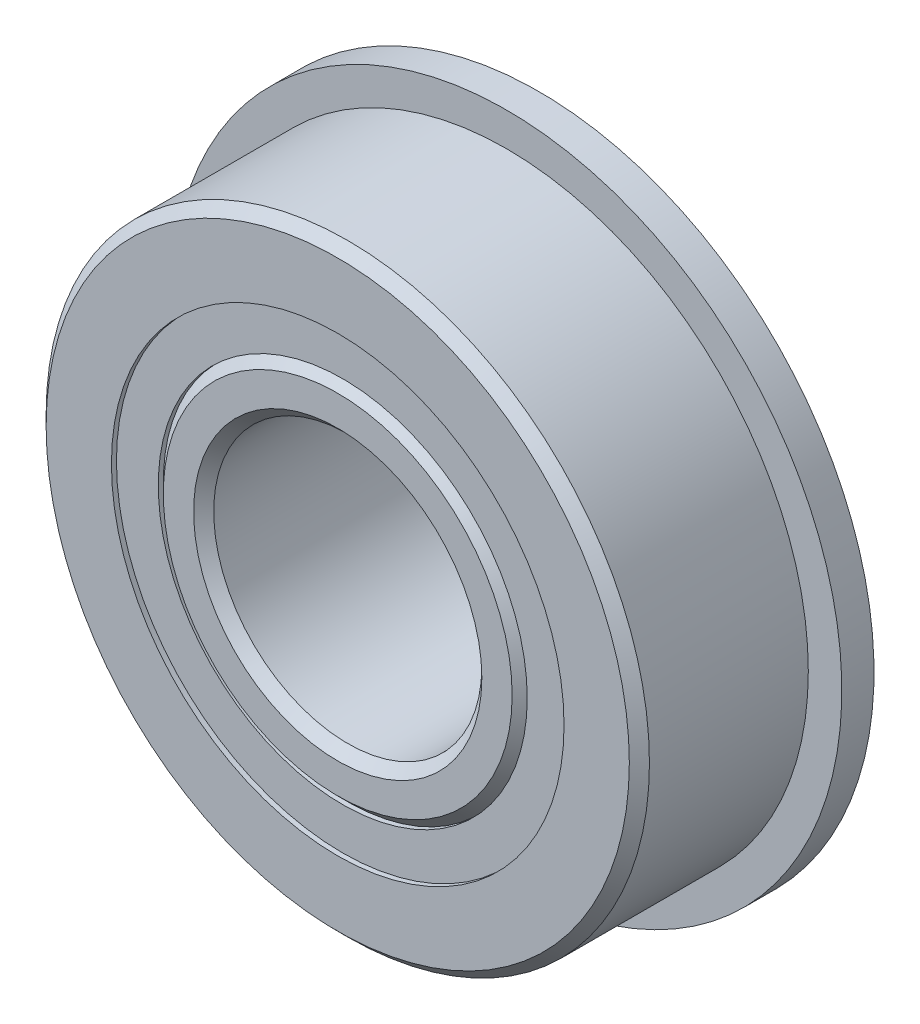
SolidWorks part; units mm, degrees
ref_plane "Front Plane" through (0, 0, 0) normal (0, 0, 1) x (1, 0, 0)
ref_plane "Top Plane" through (0, 0, 0) normal (0, 1, 0) x (1, 0, 0)
ref_plane "Right Plane" through (0, 0, 0) normal (1, 0, 0) x (0, 0, -1)
sketch "Sketch1" plane through (0, 0, 0) normal (1, 0, 0) x (0, 0, -1)
  line L0 (-4.7625, 0) -> (4.7625, 0) construction
  line L1 (0, 14.2875) -> (0, -14.2875) construction
  line L2 (4.2863, 14.2875) -> (-4.2862, 14.2875)
  line L3 (-4.2862, 14.2875) -> (-4.7625, 13.8112)
  line L4 (-4.7625, 13.8112) -> (-4.7625, 10.7188)
  line L5 (-4.7625, 10.7188) -> (-2.3474, 10.7188)
  line L6 (4.7625, 10.7188) -> (2.3474, 10.7188)
  line L7 (4.7625, 13.8112) -> (4.7625, 10.7188)
  line L8 (4.2863, 14.2875) -> (4.7625, 13.8112)
  line L9 (0, 14.2875) -> (0, 10.3187) construction
  line L10 (0, 10.3187) -> (0, 6.35) construction
  line L11 (4.7625, 8.7376) -> (4.7625, -8.7376) construction
  line L12 (-4.7625, 6.35) -> (4.7625, 6.35) construction
  line L13 (0, 7.9375) -> (0, 6.35) construction
  line L14 (0, 12.7) -> (0, 14.2875) construction
  line L15 (4.7625, 8.7376) -> (0, 8.7376) construction
  circle A1 centre (0, 10.3187) radius 2.3813 construction
  arc A2 (-2.3474, 10.7188) -> (2.3474, 10.7188) centre (0, 10.3187) cw
  point P14 (0, 6.35)
  point P22 (0, 7.9375)
  point P23 (0, 12.7)
  dimension "D3" = 4.7625
  dimension "Width" = 9.525
  dimension "OD" = 28.575
  dimension "D1" = 45
  dimension "D2" = 0.4763
  dimension "D4" = 17.4752
  dimension "D5" = 3.9624
  dimension "D6" = 1.9812
revolve "Revolve1" add sketch "Sketch1" angle 360 about L0
sketch "Sketch3" plane through (0, 0, 0) normal (1, 0, 0) x (0, 0, -1)
  line L1 (-4.7625, 13.8112) -> (-4.7625, 10.7188) construction
  line L2 (-4.2862, 14.2875) -> (-4.7625, 13.8112) construction
  line L3 (-4.7625, 9.9187) -> (-4.7625, 6.8262) construction
  line L4 (-4.7625, 6.8262) -> (-4.7625, 8.2614)
  line L5 (-4.7625, 6.8262) -> (-4.2862, 6.35)
  line L6 (-4.2862, 6.35) -> (5.8865, 6.35)
  line L7 (-4.7625, 13.8112) -> (-4.7625, -13.8112) construction
  line L8 (5.8865, 6.35) -> (6.3627, 6.8262)
  line L9 (0, 0) -> (6.3627, 0) construction
  line L13 (4.2863, 14.2875) -> (4.7625, 13.8112) construction
  line L14 (-4.7625, 8.2614) -> (-4.2862, 8.7376)
  line L15 (-4.2862, 8.7376) -> (-1.7805, 8.7376)
  line L16 (1.7805, 8.7376) -> (5.8865, 8.7376)
  line L17 (5.8865, 8.7376) -> (6.3627, 8.2614)
  line L18 (6.3627, 8.2614) -> (6.3627, 6.8262)
  circle A0 centre (0, 10.3187) radius 2.3812 construction
  arc A1 (-1.7805, 8.7376) -> (1.7805, 8.7376) centre (0, 10.3187) ccw
  dimension "D1" = 45
  dimension "Ring Wd" = 11.1252
  dimension "Inner Ring OD" = 17.4752
revolve "Revolve3" add sketch "Sketch3" angle 360 about L0
sketch "Sketch6" plane through (0, 0, 0) normal (1, 0, 0) x (0, 0, -1)
  line L1 (4.7625, 10.7188) -> (3.2385, 10.7188)
  line L2 (4.7625, 10.7188) -> (4.7625, 15.875)
  line L3 (4.7625, 15.875) -> (3.2385, 15.875)
  line L4 (3.2385, 10.7188) -> (3.2385, 15.875)
  line L5 (4.7625, 0) -> (-4.7625, 0) construction
  dimension "Flange OD" = 31.75
  dimension "Flange Thickness" = 1.524
revolve "Revolve6" add sketch "Sketch6" angle 360 about L5
sketch "Sketch4" plane through (0, 0, 0) normal (1, 0, 0) x (0, 0, -1)
  line L0 (-2.3813, 10.3187) -> (2.3813, 10.3187)
  circle A0 centre (0, 10.3187) radius 2.3812 construction
  arc A1 (2.3813, 10.3187) -> (-2.3813, 10.3187) centre (0, 10.3187) ccw
revolve "Revolve4" add sketch "Sketch4" angle 360 about L0
ref_axis "Axis1" through (0, 0, -4.7625) along (0, 0, 1)
pattern_circular "CirPattern1" count 12 every 30 about axis through (0, 0, -4.7625) along (0, 0, 1) of bodies 104
sketch "Sketch5" plane through (0, 0, 0) normal (1, 0, 0) x (0, 0, -1)
  line L0 (-4.7625, 10.7188) -> (-2.3474, 10.7188) construction
  line L1 (-4.5244, 10.7188) -> (-1.7805, 10.7188)
  line L2 (-4.5244, 10.7188) -> (-4.5244, 8.7376)
  line L3 (-4.5244, 8.7376) -> (-1.7805, 8.7376)
  line L4 (-1.7805, 10.7188) -> (-1.7805, 8.7376)
  line L6 (4.7625, 10.7188) -> (2.3474, 10.7188) construction
  line L7 (4.5244, 10.7188) -> (1.7805, 10.7188)
  line L8 (4.5244, 10.7188) -> (4.5244, 8.7376)
  line L9 (4.5244, 8.7376) -> (1.7805, 8.7376)
  line L10 (1.7805, 10.7188) -> (1.7805, 8.7376)
  line L12 (-4.2862, 14.2875) -> (-4.7625, 13.8112) construction
  line L13 (4.7625, 8.7376) -> (0, 8.7376) construction
  line L15 (-4.2862, 8.7376) -> (-1.7805, 8.7376) construction
  line L16 (4.5244, 10.7188) -> (4.5244, 14.0494) construction
  line L17 (4.2863, 14.2875) -> (4.7625, 13.8112) construction
  point P18 (-4.5244, 14.0494)
revolve "Revolve5" add sketch "Sketch5" angle 360 about L0
sketch "Sketch7" plane through (0, 0, -4.7625) normal (0, 0, -1) x (-1, 0, 0)
  line L0 (-9.7928, 12.4946) -> (-6.6121, 8.4364)
  line L1 (-6.3113, 8.6638) -> (-9.4933, 12.7237)
  circle A0 centre (0, 0) radius 15.875 construction
  circle A1 centre (0, 0) radius 10.7188 construction
  circle M3 centre (0, 0) radius 10.7188
  circle M4 centre (0, 0) radius 15.875
extrude "Cut-Extrude1" cut sketch "Sketch7" against normal blind 0.0025 contours L1 L0 M3 M4 region at (8.0529, 10.5804, -4.7625)
equation "\"D2@Sketch1\" = \"Width@Sketch1\"*.05"
equation "\"D2@CirPattern1\" = 360/\"Balls@CirPattern1\""
equation "\"D4@Sketch1\"=\"Inner Ring OD@Sketch3\""
equation "\"D3@Sketch1\"=\"Width@Sketch1\"/2"
equation "\"D6@Sketch1\"=\"D5@Sketch1\"/2"
